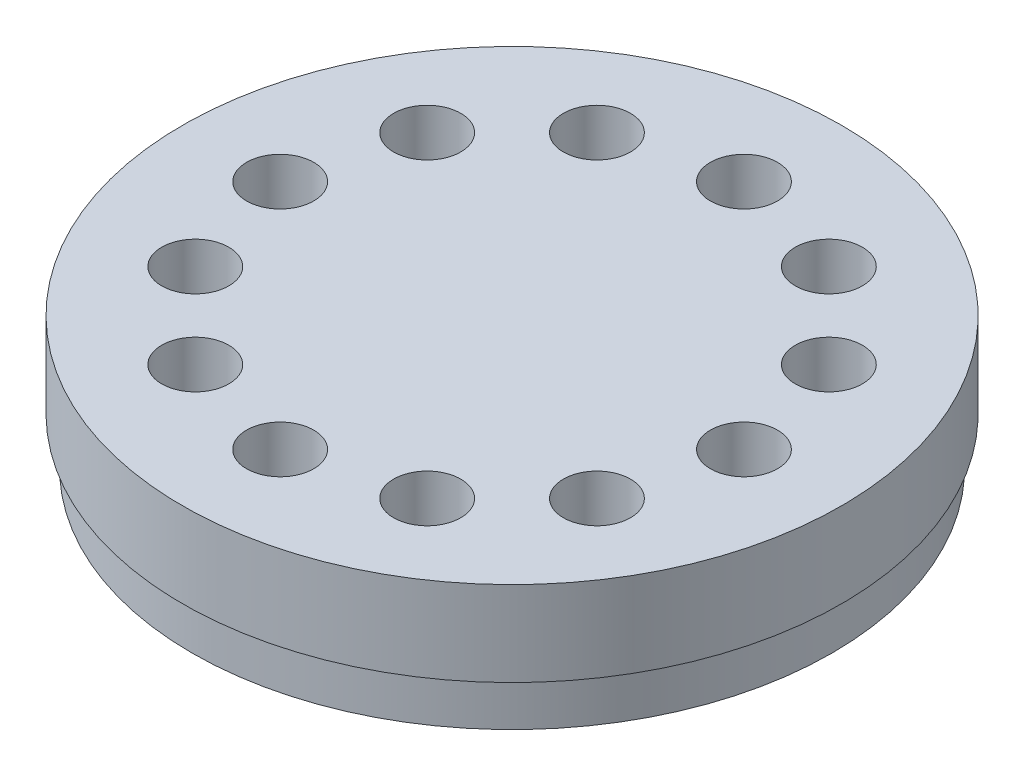
SolidWorks part; units mm, degrees
material "PVC Rigid"
ref_plane "Front Plane" through (0, 0, 0) normal (0, 0, 1) x (1, 0, 0)
ref_plane "Top Plane" through (0, 0, 0) normal (0, 1, 0) x (1, 0, 0)
ref_plane "Right Plane" through (0, 0, 0) normal (1, 0, 0) x (0, 0, -1)
sketch "Sketch1" plane through (0, 0, 0) normal (0, 0, 1) x (1, 0, 0)
  line L0 (0, 0) -> (-30.6832, 0)
  line L1 (-30.6832, 0) -> (-30.6832, -7.8994)
  line L2 (-30.6832, -7.8994) -> (-29.7942, -7.8994)
  line L3 (-29.7942, -7.8994) -> (-29.7942, -12.319)
  line L4 (-29.7942, -12.319) -> (-26.1112, -12.319)
  line L5 (-26.1112, -12.319) -> (-26.1112, -6.223)
  line L6 (-26.1112, -6.223) -> (0, -6.223)
  line L7 (0, -6.223) -> (0, 0)
  dimension "D1" = 7.8994
  dimension "D2" = 12.319
  dimension "D3" = 0.889
  dimension "D4" = 3.683
  dimension "D5" = 30.6832
  dimension "D6" = 6.096
revolve "Revolve1" add sketch "Sketch1" angle 360 about L7
sketch "Sketch2" plane through (0, 0, 0) normal (0, 1, 0) x (1, 0, 0)
  line L0 (0, 0) -> (0, 21.59) construction
  dimension "D1" = 21.59
hole_wizard "D (0.246) Diameter Hole1" positions "3DSketch1" profile "Sketch3" hole size "D" standard "Ansi Inch"
sketch3d "3DSketch1"
  point P0 (0, 0, -21.59)
sketch "Sketch3" plane through (0, 0, -21.59) normal (1, 0, 0) x (0, 0, 1)
  line L0 (0, 0) -> (0, 14.5772)
  line L1 (0, 14.5772) -> (3.1242, 12.7)
  line L2 (3.1242, 12.7) -> (3.1242, 0)
  line L5 (3.1242, 0) -> (0, 0)
  line L10 (0, 14.5772) -> (-3.1242, 12.7) construction
  line L11 (0, -6.35) -> (0, 107.95) construction
  dimension "Hole Dia." = 6.2484
  dimension "Hole Depth" = 12.7
  dimension "Drill Angle" = 118
pattern_circular "CirPattern1" count 12 over 360 about axis through (0, -6.223, 0) along (0, -1, 0) of "D (0.246) Diameter Hole1"
